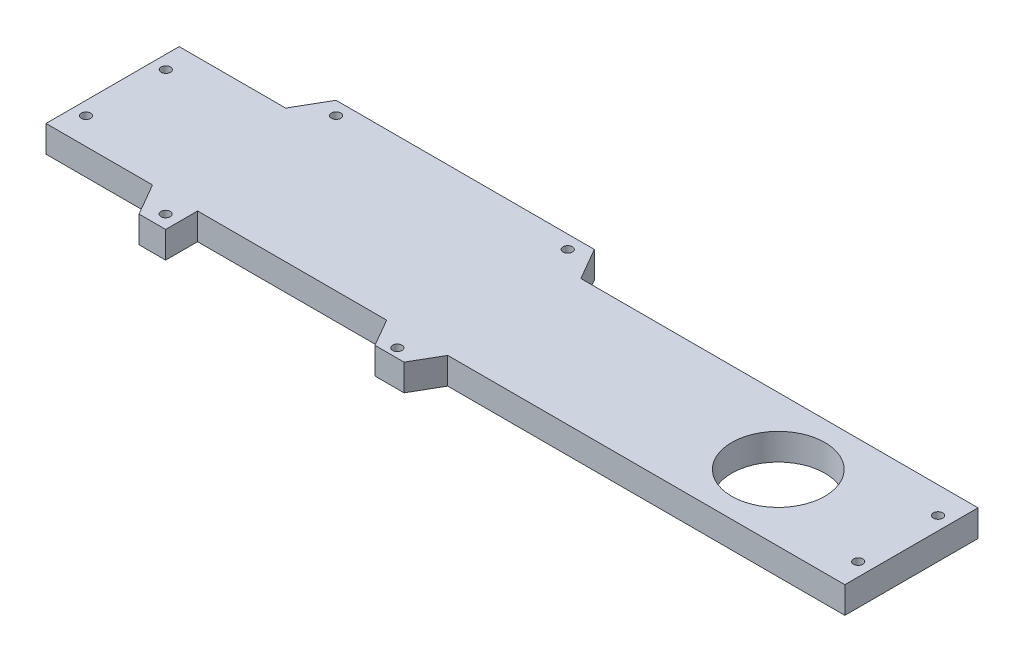
SolidWorks part; units mm, degrees
material "ABS PC"
ref_plane "Спереди" through (0, 0, 0) normal (0, 0, 1) x (1, 0, 0)
ref_plane "Сверху" through (0, 0, 0) normal (0, 1, 0) x (1, 0, 0)
ref_plane "Справа" through (0, 0, 0) normal (1, 0, 0) x (0, 0, -1)
sketch "Sketch1" plane through (0, 0, 0) normal (0, 1, 0) x (1, 0, 0)
  line L0 (40, 50) -> (46.9282, 62)
  line L1 (0, 0) -> (40, 0)
  line L2 (0, 0) -> (0, 50)
  line L3 (0, 50) -> (40, 50)
  line L4 (300, 0) -> (300, 50)
  line L5 (46.9282, 62) -> (143.9282, 62)
  line L6 (143.9282, 62) -> (150.8564, 50)
  line L7 (51.9282, 57) -> (51.9282, -7) construction
  line L10 (40, 0) -> (46.9282, -12)
  line L11 (46.9282, -12) -> (56.9282, -12)
  line L12 (56.9282, -12) -> (56.9282, 0)
  line L13 (127.9282, 0) -> (133.9282, -10.3923)
  line L14 (133.9282, -10.3923) -> (144.8564, -10.3923)
  line L15 (144.8564, -10.3923) -> (150.8564, 0)
  line L17 (150.8564, 50) -> (300, 50)
  line L18 (150.8564, 0) -> (300, 0)
  line L19 (56.9282, 0) -> (127.9282, 0)
  circle A0 centre (5, 40) radius 1.75
  circle A1 centre (5, 10) radius 1.75
  circle A2 centre (295, 10) radius 1.75
  circle A3 centre (295, 40) radius 1.75
  circle A4 centre (51.9282, 57) radius 1.75
  circle A5 centre (138.9282, 57) radius 1.75
  circle A6 centre (138.9282, -7) radius 1.75
  circle A7 centre (51.9282, -7) radius 1.75
  circle A8 centre (250, 25) radius 17.5
  point P16 (51.9282, 25)
  point P17 (0, 25)
  point P37 (51.9282, 62)
  dimension "D2" = 3.5
  dimension "D3" = 30
  dimension "D4" = 10
  dimension "D5" = 5
  dimension "D6" = 5
  dimension "D8" = 5
  dimension "D9" = 64
  dimension "D12" = 87
  dimension "D14" = 5
  dimension "D15" = 5
  dimension "D13" = 3.5
  dimension "D17" = 5
  dimension "D18" = 5
  dimension "D19" = 35
  dimension "D20" = 50
  dimension "D1" = 50
  dimension "D7" = 300
  dimension "D10" = 120
  dimension "D11" = 40
  dimension "D16" = 120
extrude "Boss-Extrude1" add sketch "Sketch1" along normal blind 10
